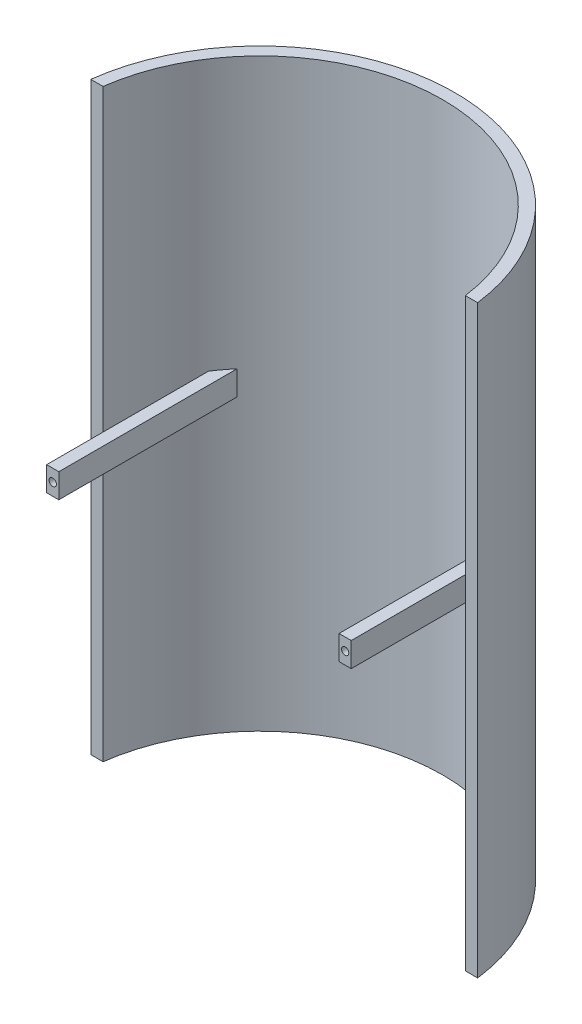
SolidWorks part; units mm, degrees
material "PUR"
ref_plane "Ön Düzlem" through (0, 0, 0) normal (0, 0, 1) x (1, 0, 0)
ref_plane "Üst Düzlem" through (0, 0, 0) normal (0, 1, 0) x (1, 0, 0)
ref_plane "Sağ Düzlem" through (0, 0, 0) normal (1, 0, 0) x (0, 0, -1)
sketch "Çizim1" plane through (0, 0, 0) normal (0, 0, 1) x (1, 0, 0)
  line L1 (-80, 120) -> (80, 120)
  line L2 (-90, 110) -> (-90, -110)
  line L3 (-80, -120) -> (80, -120)
  line L4 (90, 110) -> (90, -110)
  line L5 (-90, 120) -> (90, -120) construction
  line L6 (-90, -120) -> (90, 120) construction
  arc A0 (-90, -110) -> (-80, -120) centre (-80, -110) ccw
  arc A1 (80, -120) -> (90, -110) centre (80, -110) ccw
  arc A2 (80, 120) -> (90, 110) centre (80, 110) cw
  arc A3 (-80, 120) -> (-90, 110) centre (-80, 110) ccw
  point P0 (0, 0)
  dimension "D1" = 10
  dimension "D2" = 220
  dimension "D3" = 160
extrude "Yükseklik-Ekstrüzyon1" add sketch "Çizim1" along normal blind 70
ref_plane "Düzlem1" through (-60, 0, 0) normal (1, 0, 0) x (0, 0, -1)
sketch "Çizim3" plane through (-60, 0, 0) normal (1, 0, 0) x (0, 0, -1)
  line L0 (-5, 9) -> (-105, 9)
  line L1 (-105, 9) -> (-105, -1)
  line L2 (-105, -1) -> (-5, -1)
  line L3 (-70, 120) -> (0, 120) construction
  line L4 (-5, 9) -> (-5, -1)
  line L7 (0, 110) -> (0, -110) construction
  point P6 (0, 0)
  point P7 (0, 0)
  point P8 (0, 0)
  dimension "D1" = 111
  dimension "D2" = 10
  dimension "D3" = 100
  dimension "D4" = 5
ref_plane "Düzlem2" through (0, 0, 85) normal (0, 0, 1) x (1, 0, 0)
sketch "Çizim12" plane through (0, 120, 0) normal (0, 1, 0) x (1, 0, 0)
  line L0 (80, 0) -> (-80, 0) construction
  line L1 (90, 0) -> (80, 0) construction
  line L2 (90, -70) -> (90, 0) construction
  line L3 (80, -70) -> (90, -70) construction
  line L4 (80, -70) -> (-80, -70) construction
  line L5 (-90, -70) -> (-80, -70) construction
  line L6 (-80, 0) -> (-90, 0) construction
  line L7 (-90, -70) -> (-90, 0) construction
  line L8 (90, 0) -> (80, 0)
  line L9 (90, -70) -> (90, 0)
  line L10 (80, -70) -> (90, -70)
  line L11 (80, -70) -> (79.3725, -70)
  line L12 (-90, -70) -> (-80, -70)
  line L13 (-80, 0) -> (-90, 0)
  line L14 (-90, -70) -> (-90, 0)
  line L15 (80, 0) -> (-80, 0)
  line L16 (74.3303, -70) -> (-74.3303, -70)
  arc A0 (79.3725, -70) -> (-79.3725, -70) centre (0, -80) ccw
  arc A1 (74.3303, -70) -> (-74.3303, -70) centre (0, -80) ccw
  point P3 (0, 0)
  line M12 (80, 0) -> (-80, 0)
  line M13 (-80, 0) -> (-80, -70)
  line M14 (-80, -70) -> (80, -70)
  line M15 (80, -70) -> (80, 0)
  dimension "D1" = 160
  dimension "D2" = 150
extrude "Kes-Ekstrüzyon11" cut sketch "Çizim12" against normal blind 242 contours A0 L15 M13 M14 | L14 L12 L13 M13 | A1 M14 | A0 M14 M15 M12 | L10 L9 L8 M15 region at (85, 120, 35) region at (62.1036, 120, 17.7862) region at (-62.1036, 120, 17.7862) region at (-85, 120, 35) region at (0, 120, 42.7007)
extrude "Yükseklik-Ekstrüzyon4" add sketch "Çizim3" along normal mid plane 5
sketch "Çizim13" plane through (0, 0, 5) normal (0, 0, -1) x (-1, 0, 0)
  line L4 (62.5, -1) -> (62.5, 9)
  line L5 (62.5, 9) -> (57.5, 9)
  line L6 (57.5, 9) -> (57.5, -1)
  line L7 (57.5, -1) -> (62.5, -1)
  line L8 (62.5, -1) -> (62.5, 9)
  line L9 (62.5, 9) -> (57.5, 9)
  line L10 (57.5, 9) -> (57.5, -1)
  line L11 (57.5, -1) -> (62.5, -1)
  dimension "D1" = 0
extrude "Kes-Ekstrüzyon12" cut sketch "Çizim13" against normal up to surface (19.3785 mm away) up to face at (-60.0336, 4, 27.1909)
sketch "Çizim14" plane through (0, 0, 105) normal (0, 0, 1) x (1, 0, 0)
  line L0 (-60, -57.75) -> (-60, 57.75) construction
  line L1 (-62.5, -1) -> (-57.5, -1) construction
  circle A0 centre (-60, 4) radius 1.5
  dimension "D2" = 3
  dimension "D1" = 5
extrude "Kes-Ekstrüzyon13" cut sketch "Çizim14" against normal blind 27
mirror "Aynalama4" about plane through (0, 0, 0) normal (1, 0, 0) of "Kes-Ekstrüzyon13", "Kes-Ekstrüzyon12", "Yükseklik-Ekstrüzyon4"
